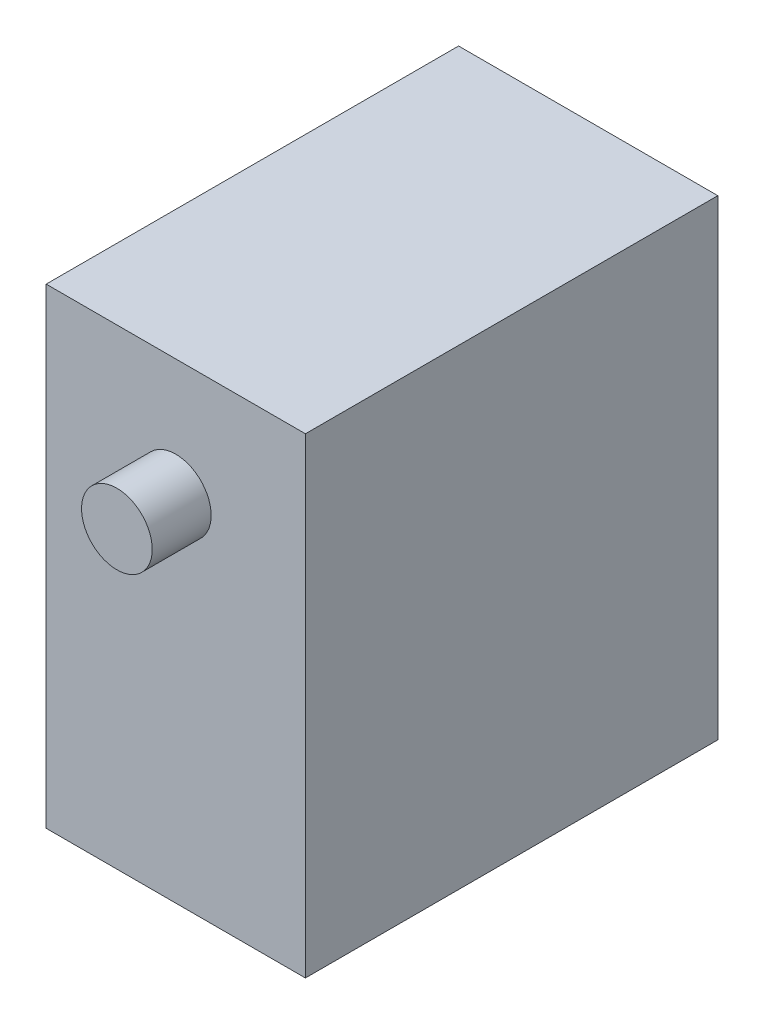
SolidWorks part; units mm, degrees
ref_plane "Front Plane" through (0, 0, 0) normal (0, 0, 1) x (1, 0, 0)
ref_plane "Top Plane" through (0, 0, 0) normal (0, 1, 0) x (1, 0, 0)
ref_plane "Right Plane" through (0, 0, 0) normal (1, 0, 0) x (0, 0, -1)
sketch "Sketch1" plane through (0, 0, 0) normal (0, 0, 1) x (1, 0, 0)
  line L0 (-22.0412, 10) -> (34.9775, 10) construction
  line L1 (11, -20) -> (-11, -20)
  line L2 (11, -20) -> (11, 20)
  line L3 (11, 20) -> (-11, 20)
  line L4 (-11, -20) -> (-11, 20)
  line L5 (11, -20) -> (-11, 20) construction
  line L6 (11, 20) -> (-11, -20) construction
  line L7 (0, 28.221) -> (0, -32.4232) construction
  circle A0 centre (0, 10) radius 3
  point P0 (0, 0)
  dimension "D4" = 6
  dimension "D1" = 22
  dimension "D2" = 40
  dimension "D3" = 30
extrude "Boss-Extrude1" add sketch "Sketch1" along normal blind 35
extrude "Boss-Extrude2" add sketch "Sketch1<2>" along normal blind 40 contours A0 region at (0, 10, 0)
sketch "Sketch1<2>" plane through (0, 0, 0) normal (0, 0, 1) x (1, 0, 0) same geometry as "Sketch1"
